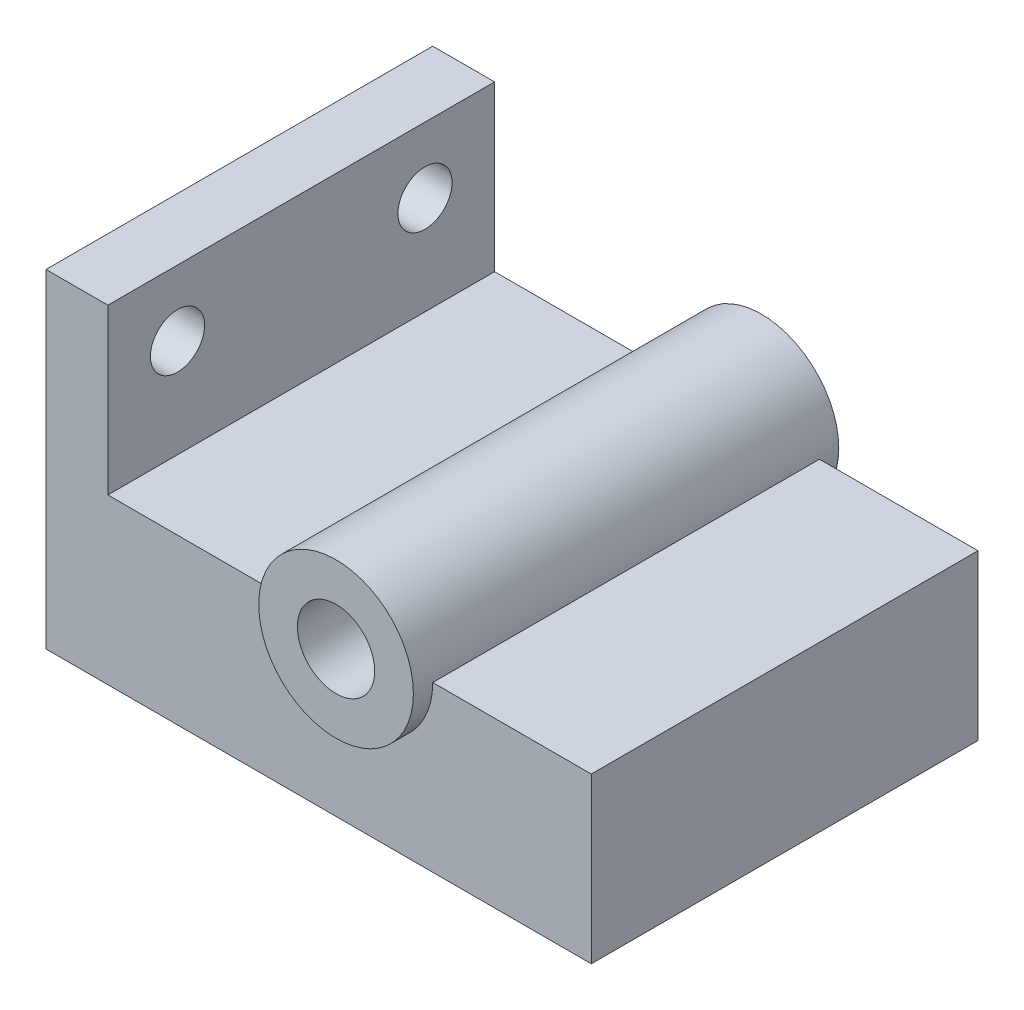
SolidWorks part; units mm, degrees
ref_plane "Front Plane" through (0, 0, 0) normal (0, 0, 1) x (1, 0, 0)
ref_plane "Top Plane" through (0, 0, 0) normal (0, 1, 0) x (1, 0, 0)
ref_plane "Right Plane" through (0, 0, 0) normal (1, 0, 0) x (0, 0, -1)
sketch "Sketch1" plane through (0, 0, 0) normal (0, 0, 1) x (1, 0, 0)
  line L0 (0, 0) -> (3581.4, 0)
  line L1 (3581.4, 0) -> (3581.4, 1079.5)
  line L2 (3581.4, 1079.5) -> (2540, 1079.5)
  line L3 (406.4, 1079.5) -> (406.4, 2159)
  line L4 (406.4, 2159) -> (0, 2159)
  line L5 (0, 2159) -> (0, 0)
  line L6 (1524, 1079.5) -> (406.4, 1079.5)
  circle A0 centre (2032, 1079.5) radius 508
  circle A1 centre (2032, 1079.5) radius 254
  dimension "D1" = 1016
  dimension "D2" = 508
  dimension "D3" = 1079.5
  dimension "D4" = 3581.4
  dimension "D5" = 406.4
  dimension "D6" = 2159
  dimension "D7" = 2032
extrude "Boss-Extrude1" add sketch "Sketch1" along normal blind 1270 and the other way blind 1270 contours A0 L6 L3 L4 L5 L0 L1 L2 region at (1587.0143, 627.5025, 0)
extrude "Boss-Extrude2" add sketch "Sketch1<3>" along normal blind 1397 and the other way blind 1397 contours A0 A1 region at (2032, 585.8684, 0)
sketch "Sketch1<3>" plane through (0, 0, 0) normal (0, 0, 1) x (1, 0, 0) same geometry as "Sketch1"
sketch "Sketch2" plane through (0, 0, 0) normal (-1, 0, 0) x (0, 0, 1)
  line L0 (-1270, 0) -> (1270, 0) construction
  line L1 (-762, 635) -> (762, 635)
  line L2 (-762, 635) -> (-762, 0)
  line L3 (-762, 0) -> (762, 0)
  line L4 (762, 635) -> (762, 0)
  point P6 (0, 635)
  dimension "D1" = 1524
  dimension "D2" = 635
extrude "Cut-Extrude1" cut sketch "Sketch2" against normal blind 3175
sketch "Sketch3" plane through (0, 0, 0) normal (-1, 0, 0) x (0, 0, 1)
  line L0 (-1270, 2159) -> (1270, 2159) construction
  circle A0 centre (-812.8, 1727.2) radius 177.8
  circle A1 centre (812.8, 1727.2) radius 177.8
  point P6 (0, 2159)
  dimension "D1" = 355.6
  dimension "D2" = 431.8
  dimension "D3" = 812.8
  dimension "D4" = 812.8
extrude "Cut-Extrude2" cut sketch "Sketch3" against normal blind 508
scale "Scale1" scale about centroid uniform scaling yes scale factor 0.03937
